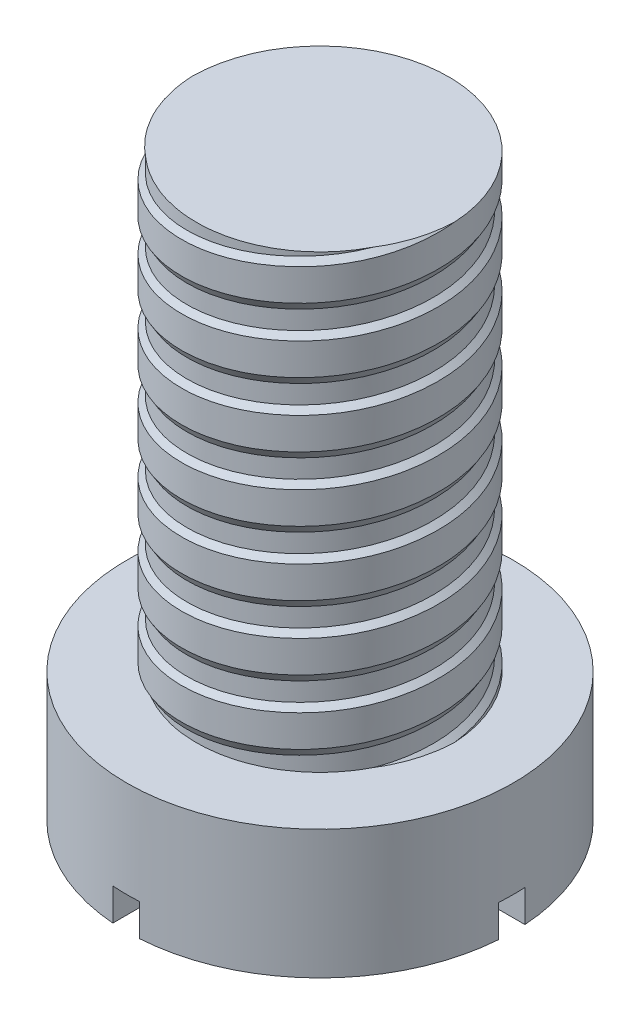
SolidWorks part; units mm, degrees
ref_plane "Front Plane" through (0, 0, 0) normal (0, 0, 1) x (1, 0, 0)
ref_plane "Top Plane" through (0, 0, 0) normal (0, 1, 0) x (1, 0, 0)
ref_plane "Right Plane" through (0, 0, 0) normal (1, 0, 0) x (0, 0, -1)
sketch "Sketch1" plane through (0, 0, 0) normal (0, 1, 0) x (1, 0, 0)
  circle A0 centre (0, 0) radius 3
  dimension "D1" = 6
extrude "Boss-Extrude1" add sketch "Sketch1" along normal blind 2
sketch "Sketch2" plane through (0, 2, 0) normal (0, 1, 0) x (1, 0, 0)
  circle A0 centre (0, 0) radius 2
  dimension "D1" = 4
extrude "Boss-Extrude2" add sketch "Sketch2" along normal blind 7
ref_plane "Plane1" through (0, 10, 0) normal (0, 1, 0) x (1, 0, 0)
sketch "Sketch3" plane through (0, 10, 0) normal (0, 1, 0) x (1, 0, 0)
  circle A0 centre (0, 0) radius 2
  dimension "D1" = 4
curve "Helix/Spiral1" pitch 1 height 8 radius 2 centre (0, 10, 0) axis (0, -1, 0) start towards (0, 0, 1)
sketch "Sketch4" plane through (0, 0, 0) normal (0, 0, 1) x (1, 0, 0)
  line L0 (2, 8.5007) -> (1.9174, 8.364)
  line L1 (1.9174, 8.364) -> (1.9174, 8.0756)
  line L2 (1.9174, 8.0756) -> (2, 7.993)
  line L3 (2, 7.993) -> (2, 8.5007)
  spline S1 degree 3 poles (-2, 10) (-2, 9.9793) (-1.8959, 9.9374) (-1.451, 9.875) (-0.7853, 9.8125) (0, 9.75) (0.7853, 9.6875) (1.451, 9.625) (1.8959, 9.5625) (2.0521, 9.5) (1.8959, 9.4375) (1.451, 9.375) (0.5634, 9.2917) (-0.5634, 9.2083) (-1.451, 9.125) (-1.8959, 9.0625) (-2.0521, 9) (-1.8959, 8.9375) (-1.451, 8.875) (-0.5634, 8.7917) (0.5634, 8.7083) (1.451, 8.625) (1.8959, 8.5625) (2.0521, 8.5) (1.8959, 8.4375) (1.451, 8.375) (0.5634, 8.2917) (-0.5634, 8.2083) (-1.451, 8.125) (-1.8959, 8.0625) (-2.0521, 8) (-1.8959, 7.9375) (-1.451, 7.875) (-0.5634, 7.7917) (0.5634, 7.7083) (1.451, 7.625) (1.8959, 7.5625) (2.0521, 7.5) (1.8959, 7.4375) (1.451, 7.375) (0.5634, 7.2917) (-0.5634, 7.2083) (-1.451, 7.125) (-1.8959, 7.0625) (-2.0521, 7) (-1.8959, 6.9375) (-1.451, 6.875) (-0.5634, 6.7917) (0.5634, 6.7083) (1.451, 6.625) (1.8959, 6.5625) (2.0521, 6.5) (1.8959, 6.4375) (1.451, 6.375) (0.5634, 6.2917) (-0.5634, 6.2083) (-1.451, 6.125) (-1.8959, 6.0625) (-2.0521, 6) (-1.8959, 5.9375) (-1.451, 5.875) (-0.5634, 5.7917) (0.5634, 5.7083) (1.451, 5.625) (1.8959, 5.5625) (2.0521, 5.5) (1.8959, 5.4375) (1.451, 5.375) (0.5634, 5.2917) (-0.5634, 5.2083) (-1.451, 5.125) (-1.8959, 5.0625) (-2.0521, 5) (-1.8959, 4.9375) (-1.451, 4.875) (-0.5634, 4.7917) (0.5634, 4.7083) (1.451, 4.625) (1.8959, 4.5625) (2.0521, 4.5) (1.8959, 4.4375) (1.451, 4.375) (0.5634, 4.2917) (-0.5634, 4.2083) (-1.451, 4.125) (-1.8959, 4.0625) (-2.0521, 4) (-1.8959, 3.9375) (-1.451, 3.875) (-0.5634, 3.7917) (0.5634, 3.7083) (1.451, 3.625) (1.8959, 3.5625) (2.0521, 3.5) (1.8959, 3.4375) (1.451, 3.375) (0.5634, 3.2917) (-0.5634, 3.2083) (-1.451, 3.125) (-1.8959, 3.0625) (-2.0521, 3) (-1.8959, 2.9375) (-1.451, 2.875) (-0.5634, 2.7917) (0.5634, 2.7083) (1.451, 2.625) (1.8959, 2.5625) (2.0521, 2.5) (1.8959, 2.4375) (1.451, 2.375) (0.7853, 2.3125) (0, 2.25) (-0.7853, 2.1875) (-1.451, 2.125) (-1.8959, 2.0626) (-2, 2.0207) (-2, 2) knots 0 0 0 0 0.007813 0.015625 0.023438 0.03125 0.039063 0.046875 0.054688 0.0625 0.070313 0.078125 0.085938 0.101563 0.109375 0.117188 0.125 0.132813 0.140625 0.148438 0.164063 0.171875 0.179688 0.1875 0.195313 0.203125 0.210938 0.226563 0.234375 0.242188 0.25 0.257813 0.265625 0.273438 0.289063 0.296875 0.304688 0.3125 0.320313 0.328125 0.335938 0.351563 0.359375 0.367188 0.375 0.382813 0.390625 0.398438 0.414063 0.421875 0.429688 0.4375 0.445313 0.453125 0.460938 0.476563 0.484375 0.492188 0.5 0.507813 0.515625 0.523438 0.539063 0.546875 0.554688 0.5625 0.570313 0.578125 0.585938 0.601563 0.609375 0.617188 0.625 0.632813 0.640625 0.648438 0.664063 0.671875 0.679688 0.6875 0.695313 0.703125 0.710938 0.726563 0.734375 0.742188 0.75 0.757813 0.765625 0.773438 0.789063 0.796875 0.804688 0.8125 0.820313 0.828125 0.835938 0.851563 0.859375 0.867188 0.875 0.882813 0.890625 0.898438 0.914063 0.921875 0.929688 0.9375 0.945313 0.953125 0.960938 0.96875 0.976563 0.984375 0.992188 1 1 1 1 construction
sweep "Cut-Sweep1" cut profiles "Sketch4" path "Helix/Spiral1" align with end faces yes
sketch "Sketch5" plane through (0, 0, 0) normal (0, -1, 0) x (1, 0, 0)
  line L0 (0, 3.2089) -> (-0.2259, 3.2089)
  line L1 (-0.2259, 3.2089) -> (-0.2259, -3.1503)
  line L2 (-0.2259, -3.1503) -> (0.1925, -3.1503)
  line L3 (0.1925, -3.1503) -> (0.1925, 3.2089)
  line L4 (0.1925, 3.2089) -> (0, 3.2089)
  line L5 (-3.4223, 0) -> (-3.4223, 0.2217)
  line L6 (-3.4223, 0.2217) -> (3.2717, 0.2217)
  line L7 (3.2717, 0.2217) -> (3.2717, -0.1883)
  line L8 (3.2717, -0.1883) -> (-3.4223, -0.1883)
  line L9 (-3.4223, -0.1883) -> (-3.4223, 0)
  circle M6 centre (0, 0) radius 3
extrude "Cut-Extrude1" cut sketch "Sketch5" against normal blind 0.5 contours L8 L1 L6 M6 | L8 L6 L3 M6 | L8 L3 L6 L1 | L1 L6 L3 M6 | L3 L8 L1 M6 region at (-0.0167, 0, 1.6096) region at (-0.0167, 0, 0.0167) region at (-1.6118, 0, 0.0167) region at (1.595, 0, 0.0167) region at (-0.0167, 0, -1.5929)
